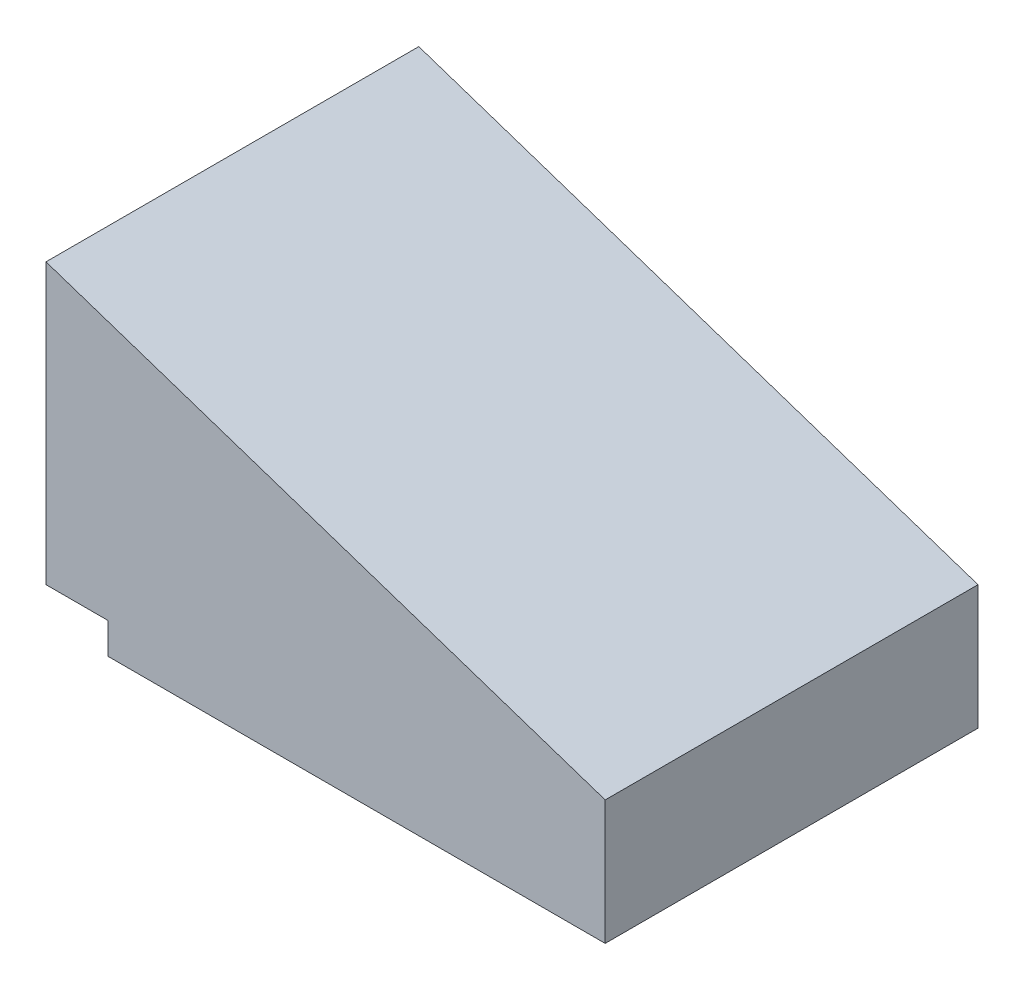
SolidWorks part; units mm, degrees
material "Acrylic (Medium-high impact)"
ref_plane "Front Plane" through (0, 0, 0) normal (0, 0, 1) x (1, 0, 0)
ref_plane "Top Plane" through (0, 0, 0) normal (0, 1, 0) x (1, 0, 0)
ref_plane "Right Plane" through (0, 0, 0) normal (1, 0, 0) x (0, 0, -1)
sketch "Sketch3" plane through (0, 0, 0) normal (0, 0, 1) x (1, 0, 0)
  line L0 (-228.6, 127) -> (0, 50.8)
  line L1 (0, 0) -> (-228.6, 0)
  line L2 (0, 0) -> (0, 50.8)
  line L4 (-228.6, 0) -> (-228.6, 127)
  dimension "D1" = 50.8
  dimension "D2" = 127
  dimension "D3" = 228.6
extrude "Boss-Extrude2" add sketch "Sketch3" along normal blind 152.4
shell "Shell1" thickness 1.5875 removed face at (-114.3, 0, 76.2)
sketch "Sketch4" plane through (0, 0, 0) normal (0, 0, -1) x (-1, 0, 0)
  line L1 (228.6, 0) -> (203.2, 0)
  line L2 (228.6, 0) -> (228.6, 12.7)
  line L3 (228.6, 12.7) -> (203.2, 12.7)
  line L4 (203.2, 0) -> (203.2, 12.7)
  dimension "D1" = 12.7
  dimension "D2" = 25.4
extrude "Cut-Extrude1" cut sketch "Sketch4" against normal blind 152.4
